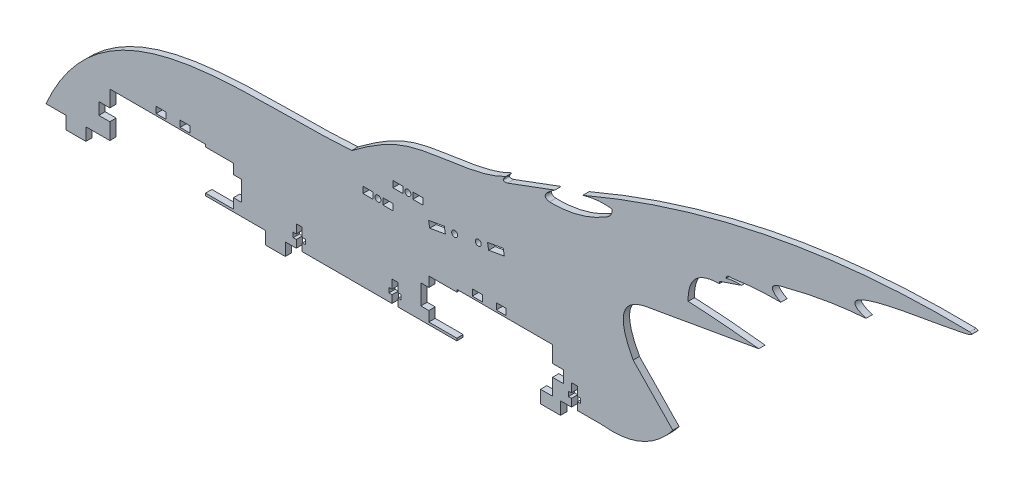
SolidWorks part; units mm, degrees
ref_plane "前视基准面" through (0, 0, 0) normal (0, 0, 1) x (1, 0, 0)
ref_plane "上视基准面" through (0, 0, 0) normal (0, 1, 0) x (1, 0, 0)
ref_plane "右视基准面" through (0, 0, 0) normal (1, 0, 0) x (0, 0, -1)
sketch "Sketch1" plane through (0, 0, 0) normal (0, 0, 1) x (1, 0, 0)
  line L0 (-360, 0) -> (360, 0) construction
  line L1 (-19.5671, 50.1455) -> (753.6757, 55.0373) construction
  line L2 (-32.114, 89.2833) -> (541.2194, 89.2833) construction
sketch "Sketch2" plane through (0, 0, 0) normal (0, 0, 1) x (1, 0, 0)
  line L0 (-171.469, -34.0766) -> (107.0727, -34.0766)
  spline S0 degree 2 poles (291.7809, 98.4714) (190.6089, 100.5394) (97.7379, 60.7759) knots 0 0 0 1 1 1
  spline S1 degree 2 poles (97.7379, 60.7759) (104.9288, 63.0011) (112.3796, 62.1565) knots 0 0 0 1 1 1
  spline S2 degree 2 poles (112.3796, 62.1565) (112.7301, 59.0518) (109.5504, 57.3117) knots 0 0 0 1 1 1
  spline S3 degree 2 poles (109.5504, 57.3117) (96.53, 49.2469) (81.0586, 49.5528) knots 0 0 0 1 1 1
  spline S4 degree 2 poles (81.0586, 49.5528) (75.6423, 50.628) (83.6966, 55.9983) knots 0 0 0 1 1 1
  spline S5 degree 1 poles (83.6966, 55.9983) (60.0234, 47.198) knots 0 0 1 1
  spline S6 degree 2 poles (60.0234, 47.198) (56.1503, 46.2452) (59.1238, 49.6133) knots 0 0 0 1 1 1
  spline S7 degree 3 poles (59.1238, 49.6133) (44.2925, 41.9215) (13.2093, 43.4053) (-7.7072, 29.9938) (-18.1066, 22.3013) knots 0 0 0 0 0.606339 1 1 1 1
  spline S8 degree 3 poles (-18.1066, 22.3013) (-73.3001, 18.1787) (-142.3815, 32.9288) (-171.469, -34.0766) knots 0 0 0 0 1 1 1 1
  spline S9 degree 2 poles (107.0727, -34.0766) (128.9682, -36.583) (142.8921, -18.7155) knots 0 0 0 1 1 1
  spline S10 degree 2 poles (166.2115, 56.6) (150.1116, 56.4482) (150.5886, 41.1327) knots 0 0 0 1 1 1
  spline S11 degree 2 poles (150.5886, 41.1327) (168.3325, 40.2418) (185.983, 38.2447) knots 0 0 0 1 1 1
  spline S12 degree 1 poles (185.983, 38.2447) (129.8121, 28.3469) knots 0 0 1 1
  spline S13 degree 2 poles (129.8121, 28.3469) (110.3675, 24.8357) (122.9996, 1.8225) knots 0 0 0 1 1 1
  spline S14 degree 1 poles (122.9996, 1.8225) (142.8921, -18.7155) knots 0 0 1 1
  spline S25 degree 1 poles (166.2115, 56.6) (166.2327, 57.6697) knots 0 0 1 1
  spline S26 degree 1 poles (166.2327, 57.6697) (177.2433, 61.4033) knots 0 0 1 1
  spline S27 degree 2 poles (177.2433, 61.4033) (173.3395, 61.7966) (169.6271, 60.6108) knots 0 0 0 1 1 1
  spline S28 degree 2 poles (169.6271, 60.6108) (169.7629, 62.5449) (172.4023, 62.1565) knots 0 0 0 1 1 1
  spline S29 degree 2 poles (172.4023, 62.1565) (184.6173, 64.0415) (197.0298, 63.9473) knots 0 0 0 1 1 1
  spline S30 degree 2 poles (197.0298, 63.9473) (187.7347, 69.0696) (198.9644, 71.4021) knots 0 0 0 1 1 1
  spline S31 degree 2 poles (198.9644, 71.4021) (219.0035, 76.7865) (239.7646, 78.3299) knots 0 0 0 1 1 1
  spline S32 degree 3 poles (291.7809, 98.4714) (303.0909, 95.7177) (210.844, 88.0264) (239.7646, 78.3299) knots 0 0 0 0 1 1 1 1
extrude "Boss-Extrude1" add sketch "Sketch2" along normal blind 3.175
sketch "Sketch3" plane through (0, 0, 3.175) normal (0, 0, 1) x (1, 0, 0)
  line L0 (-156.469, -23.0187) -> (-156.469, -49.8356) construction
  line L1 (-161.469, -34.0766) -> (-151.469, -34.0766)
  line L2 (-171.469, -34.0766) -> (107.0727, -34.0766) construction
  line L3 (-161.469, -34.0766) -> (-161.469, -40.4266)
  line L4 (-161.469, -40.4266) -> (-151.469, -40.4266)
  line L5 (-151.469, -40.4266) -> (-151.469, -34.0766)
  line L6 (-106.469, -7.8183) -> (-106.469, -55.0925) construction
  line L7 (-56.469, -23.0187) -> (-56.469, -49.8356) construction
  line L8 (-61.469, -40.4266) -> (-61.469, -34.0766)
  line L9 (-51.469, -40.4266) -> (-61.469, -40.4266)
  line L10 (-51.469, -34.0766) -> (-51.469, -40.4266)
  line L11 (-51.469, -34.0766) -> (-61.469, -34.0766)
  line L12 (-37.469, -5.6354) -> (-37.469, -55.0925) construction
  line L13 (81.531, -23.0187) -> (81.531, -49.8356) construction
  line L14 (76.531, -40.4266) -> (76.531, -34.0766)
  line L15 (86.531, -40.4266) -> (76.531, -40.4266)
  line L16 (86.531, -34.0766) -> (86.531, -40.4266)
  line L17 (86.531, -34.0766) -> (76.531, -34.0766)
  point P6 (-156.469, -34.0766)
  dimension "D1" = 10
  dimension "D2" = 15
  dimension "D3" = 6.35
  dimension "D4" = 100
  dimension "D5" = 238
extrude "Boss-Extrude2" add sketch "Sketch3" against normal blind 3.175
sketch "Sketch4" plane through (0, 0, 0) normal (0, 0, 1) x (1, 0, 0)
  line L0 (-8.7353, 21.0767) -> (49.2725, 25.4437)
  spline S0 degree 3 poles (55.4358, 40.7209) (33.0546, 40.3601) (7.8741, 39.273) (-8.7353, 21.0767) knots 0 0 0 0 1 1 1 1
  spline S1 degree 3 poles (55.4358, 40.7209) (56.7107, 34.9555) (51.7522, 29.9519) (49.2725, 25.4437) knots 0 0 0 0 1 1 1 1
extrude "Cut-Extrude1" cut sketch "Sketch4" along normal blind 1
sketch "Sketch5" plane through (0, 0, 3.175) normal (0, 0, 1) x (1, 0, 0)
  line L0 (-44.469, -4.9545) -> (-44.469, -56.9042) construction
  line L1 (-45.969, -34.0766) -> (-42.969, -34.0766)
  line L2 (-151.469, -34.0766) -> (-61.469, -34.0766) construction
  line L3 (-45.969, -34.0766) -> (-45.969, -30.2766)
  line L4 (-45.969, -23.4266) -> (-42.969, -23.4266)
  line L5 (-42.969, -23.4266) -> (-42.969, -27.8766)
  line L6 (-161.469, -40.4266) -> (-151.469, -40.4266) construction
  line L7 (-41.419, -27.8766) -> (-41.419, -30.2766)
  line L8 (-47.519, -27.8766) -> (-47.519, -30.2766)
  line L9 (-47.519, -27.8766) -> (-45.969, -27.8766)
  line L10 (-47.519, -30.2766) -> (-45.969, -30.2766)
  line L11 (-47.519, -29.0766) -> (-93.8427, -29.0766) construction
  line L12 (-161.469, -34.0766) -> (-161.469, -40.4266) construction
  line L13 (-42.969, -27.8766) -> (-41.419, -27.8766)
  line L14 (-42.969, -30.2766) -> (-41.419, -30.2766)
  line L15 (-45.969, -27.8766) -> (-45.969, -23.4266)
  line L16 (-42.969, -30.2766) -> (-42.969, -34.0766)
  line L17 (-20.469, -10.7451) -> (-20.469, -65.5516) construction
  line L18 (3.531, -4.9545) -> (3.531, -56.9042) construction
  line L19 (2.031, -30.2766) -> (2.031, -34.0766)
  line L20 (5.031, -27.8766) -> (5.031, -23.4266)
  line L21 (2.031, -30.2766) -> (0.481, -30.2766)
  line L22 (2.031, -27.8766) -> (0.481, -27.8766)
  line L23 (6.581, -30.2766) -> (5.031, -30.2766)
  line L24 (6.581, -27.8766) -> (5.031, -27.8766)
  line L25 (6.581, -27.8766) -> (6.581, -30.2766)
  line L26 (0.481, -27.8766) -> (0.481, -30.2766)
  line L27 (2.031, -23.4266) -> (2.031, -27.8766)
  line L28 (5.031, -23.4266) -> (2.031, -23.4266)
  line L29 (5.031, -34.0766) -> (5.031, -30.2766)
  line L30 (5.031, -34.0766) -> (2.031, -34.0766)
  line L31 (24.531, -8.6696) -> (24.531, -64.6722) construction
  line L32 (93.531, -4.9545) -> (93.531, -56.9042) construction
  line L33 (92.031, -30.2766) -> (92.031, -34.0766)
  line L34 (95.031, -27.8766) -> (95.031, -23.4266)
  line L35 (92.031, -30.2766) -> (90.481, -30.2766)
  line L36 (92.031, -27.8766) -> (90.481, -27.8766)
  line L37 (96.581, -30.2766) -> (95.031, -30.2766)
  line L38 (96.581, -27.8766) -> (95.031, -27.8766)
  line L39 (96.581, -27.8766) -> (96.581, -30.2766)
  line L40 (90.481, -27.8766) -> (90.481, -30.2766)
  line L41 (92.031, -23.4266) -> (92.031, -27.8766)
  line L42 (95.031, -23.4266) -> (92.031, -23.4266)
  line L43 (95.031, -34.0766) -> (95.031, -30.2766)
  line L44 (95.031, -34.0766) -> (92.031, -34.0766)
  point P6 (-44.469, -34.0766)
  dimension "D1" = 3
  dimension "D2" = 17
  dimension "D3" = 6.1
  dimension "D4" = 5
  dimension "D5" = 117
  dimension "D6" = 2.4
  dimension "D7" = 165
  dimension "D8" = 255
extrude "Cut-Extrude2" cut sketch "Sketch5" against normal through all
sketch "Sketch7" plane through (0, 0, 3.175) normal (0, 0, 1) x (1, 0, 0)
  line L0 (-91.469, -32.8766) -> (-77.469, -32.8766)
  line L1 (-139.469, -34.0766) -> (-139.469, -25.8766)
  line L2 (-151.469, -34.0766) -> (-61.469, -34.0766) construction
  line L3 (-139.469, -11.6766) -> (-91.469, -11.6766)
  line L4 (-91.469, -11.6766) -> (-91.469, -12.8766)
  line L5 (-139.469, -34.0766) -> (-91.469, -34.0766)
  line L6 (-155.6863, -22.8766) -> (-79.2758, -22.8766) construction
  line L7 (-91.469, -12.8766) -> (-77.469, -12.8766)
  line L8 (-77.469, -12.8766) -> (-77.469, -17.8766)
  line L9 (-91.469, -32.8766) -> (-91.469, -34.0766)
  line L10 (-139.469, -19.8766) -> (-144.969, -19.8766)
  line L11 (-139.469, -25.8766) -> (-144.969, -25.8766)
  line L12 (-144.969, -19.8766) -> (-144.969, -25.8766)
  line L13 (-139.469, -19.8766) -> (-139.469, -11.6766)
  line L14 (-77.469, -17.8766) -> (-73.469, -17.8766)
  line L15 (-77.469, -27.8766) -> (-73.469, -27.8766)
  line L16 (-73.469, -17.8766) -> (-73.469, -27.8766)
  line L17 (-77.469, -27.8766) -> (-77.469, -32.8766)
  line L18 (-28.469, 4.1122) -> (-28.469, -62.6854) construction
  line L19 (98.7482, -22.8766) -> (22.3377, -22.8766) construction
  line L20 (20.531, -27.8766) -> (20.531, -32.8766)
  line L21 (16.531, -17.8766) -> (16.531, -27.8766)
  line L22 (20.531, -27.8766) -> (16.531, -27.8766)
  line L23 (20.531, -17.8766) -> (16.531, -17.8766)
  line L24 (82.531, -19.8766) -> (82.531, -11.6766)
  line L25 (88.031, -19.8766) -> (88.031, -25.8766)
  line L26 (82.531, -25.8766) -> (88.031, -25.8766)
  line L27 (82.531, -19.8766) -> (88.031, -19.8766)
  line L28 (34.531, -32.8766) -> (34.531, -34.0766)
  line L29 (20.531, -12.8766) -> (20.531, -17.8766)
  line L30 (34.531, -12.8766) -> (20.531, -12.8766)
  line L31 (82.531, -34.0766) -> (34.531, -34.0766)
  line L32 (34.531, -11.6766) -> (34.531, -12.8766)
  line L33 (82.531, -11.6766) -> (34.531, -11.6766)
  line L34 (82.531, -34.0766) -> (82.531, -25.8766)
  line L35 (34.531, -32.8766) -> (20.531, -32.8766)
  line L36 (-120.2067, -9.1491) -> (-44.1643, -9.1491) construction
  line L37 (-107.769, -0.3828) -> (-107.769, -8.179) construction
  line L38 (-111.269, -10.7366) -> (-116.269, -10.7366)
  line L39 (-111.269, -10.7366) -> (-111.269, -7.5616)
  line L40 (-111.269, -7.5616) -> (-116.269, -7.5616)
  line L41 (-116.269, -10.7366) -> (-116.269, -7.5616)
  line L42 (-111.269, -10.7366) -> (-116.269, -7.5616) construction
  line L43 (-111.269, -7.5616) -> (-116.269, -10.7366) construction
  line L44 (-104.269, -7.5616) -> (-99.269, -10.7366) construction
  line L45 (-104.269, -10.7366) -> (-99.269, -7.5616) construction
  line L46 (-99.269, -10.7366) -> (-99.269, -7.5616)
  line L47 (-104.269, -7.5616) -> (-99.269, -7.5616)
  line L48 (-104.269, -10.7366) -> (-104.269, -7.5616)
  line L49 (-104.269, -10.7366) -> (-99.269, -10.7366)
  line L50 (47.331, -10.7366) -> (42.331, -7.5616) construction
  line L51 (47.331, -7.5616) -> (42.331, -10.7366) construction
  line L52 (54.331, -7.5616) -> (59.331, -10.7366) construction
  line L53 (54.331, -10.7366) -> (59.331, -7.5616) construction
  line L54 (47.331, -10.7366) -> (42.331, -10.7366)
  line L55 (47.331, -10.7366) -> (47.331, -7.5616)
  line L56 (47.331, -7.5616) -> (42.331, -7.5616)
  line L57 (42.331, -10.7366) -> (42.331, -7.5616)
  line L58 (59.331, -10.7366) -> (59.331, -7.5616)
  line L59 (54.331, -7.5616) -> (59.331, -7.5616)
  line L60 (54.331, -10.7366) -> (54.331, -7.5616)
  line L61 (54.331, -10.7366) -> (59.331, -10.7366)
  point P43 (-113.769, -9.1491)
  point P54 (-101.769, -9.1491)
  point P63 (44.831, -9.1491)
  point P64 (56.831, -9.1491)
  dimension "D3" = 48
  dimension "D1" = 32
  dimension "D2" = 22.4
  dimension "D4" = 20
  dimension "D5" = 14
  dimension "D6" = 6
  dimension "D7" = 5.5
  dimension "D8" = 4
  dimension "D9" = 10
  dimension "D10" = 90
  dimension "D11" = 12
  dimension "D12" = 23.2
  dimension "D13" = 0.94
  dimension "D14" = 3.175
  dimension "D15" = 5
extrude "Cut-Extrude3" cut sketch "Sketch7" against normal through all
sketch "Sketch8" plane through (0, 0, 0) normal (0, 0, -1) x (-1, 0, 0)
  line L0 (0, 0) -> (0, 6) construction
  line L1 (0, 6) -> (-41.3619, 13.2932) construction
  line L2 (-39.3923, 12.9459) -> (-37.8172, 21.8786) construction
  line L3 (-20.4053, 11.21) -> (-20.9566, 8.0832)
  line L4 (-20.9566, 8.0832) -> (-28.8351, 9.4724)
  line L5 (-28.8351, 9.4724) -> (-28.2838, 12.5992)
  line L6 (-28.2838, 12.5992) -> (-20.4053, 11.21)
  line L7 (-24.3445, 11.9046) -> (-23.2344, 18.2003) construction
  line L10 (-49.9495, 16.4194) -> (-50.5009, 13.2927)
  line L12 (-58.3793, 14.6819) -> (-50.5009, 13.2927)
  line L13 (-53.8888, 17.114) -> (-52.7787, 23.4098) construction
  line L14 (-58.3793, 14.6819) -> (-57.828, 17.8086)
  line L15 (-49.9495, 16.4194) -> (-57.828, 17.8086)
  circle A0 centre (-33.4835, 11.904) radius 1.5
  circle A1 centre (-45.3012, 13.9878) radius 1.5
  point P10 (-20.681, 9.6466)
  dimension "D7" = 3
  dimension "D1" = 6
  dimension "D2" = 100
  dimension "D3" = 40
  dimension "D4" = 8
  dimension "D5" = 3.175
  dimension "D6" = 30
  dimension "D8" = 12
extrude "Cut-Extrude4" cut sketch "Sketch8" against normal through all
sketch "Sketch11" plane through (0, 0, 3.175) normal (0, 0, 1) x (1, 0, 0)
  line L0 (10, 32.0127) -> (10, 0) construction
  line L1 (-16.2629, 18) -> (22.3224, 18) construction
  line L2 (2.5, 19.5875) -> (7.5, 16.4125) construction
  line L3 (17.5, 16.4125) -> (12.5, 16.4125)
  line L4 (17.5, 16.4125) -> (17.5, 19.5875)
  line L5 (17.5, 19.5875) -> (12.5, 19.5875)
  line L6 (12.5, 16.4125) -> (12.5, 19.5875)
  line L7 (17.5, 16.4125) -> (12.5, 19.5875) construction
  line L8 (17.5, 19.5875) -> (12.5, 16.4125) construction
  line L9 (2.5, 16.4125) -> (7.5, 19.5875) construction
  line L10 (7.5, 16.4125) -> (7.5, 19.5875)
  line L11 (2.5, 19.5875) -> (7.5, 19.5875)
  line L12 (2.5, 16.4125) -> (2.5, 19.5875)
  line L13 (2.5, 16.4125) -> (7.5, 16.4125)
  line L14 (-5, 12.4125) -> (-5, -3.1137) construction
  line L15 (-20.9752, 8) -> (1.55, 8) construction
  line L16 (-12.5, 6.4125) -> (-7.5, 6.4125)
  line L17 (-12.5, 6.4125) -> (-12.5, 9.5875)
  line L18 (2.5, 6.4125) -> (-2.5, 9.5875) construction
  line L19 (-7.5, 6.4125) -> (-7.5, 9.5875)
  line L20 (-12.5, 9.5875) -> (-7.5, 6.4125) construction
  line L21 (-12.5, 9.5875) -> (-7.5, 9.5875)
  line L22 (2.5, 9.5875) -> (-2.5, 6.4125) construction
  line L23 (-12.5, 6.4125) -> (-7.5, 9.5875) construction
  line L24 (2.5, 9.5875) -> (-2.5, 9.5875)
  line L25 (-2.5, 6.4125) -> (-2.5, 9.5875)
  line L26 (2.5, 6.4125) -> (2.5, 9.5875)
  line L27 (2.5, 6.4125) -> (-2.5, 6.4125)
  circle A0 centre (10, 18) radius 1.5
  circle A1 centre (-5, 8) radius 1.5
  point P4 (15, 18)
  point P13 (5, 18)
  point P24 (0, 8)
  point P29 (-10, 8)
  point P32 (-12.5, 8)
  dimension "D4" = 3
  dimension "D8" = 3
  dimension "D1" = 3.175
  dimension "D2" = 5
  dimension "D3" = 5
  dimension "D5" = 5
  dimension "D6" = 3.175
  dimension "D7" = 10
  dimension "D9" = 5
  dimension "D10" = 18
  dimension "D11" = 8
  dimension "D12" = 10
extrude "Cut-Extrude5" cut sketch "Sketch11" against normal through all
